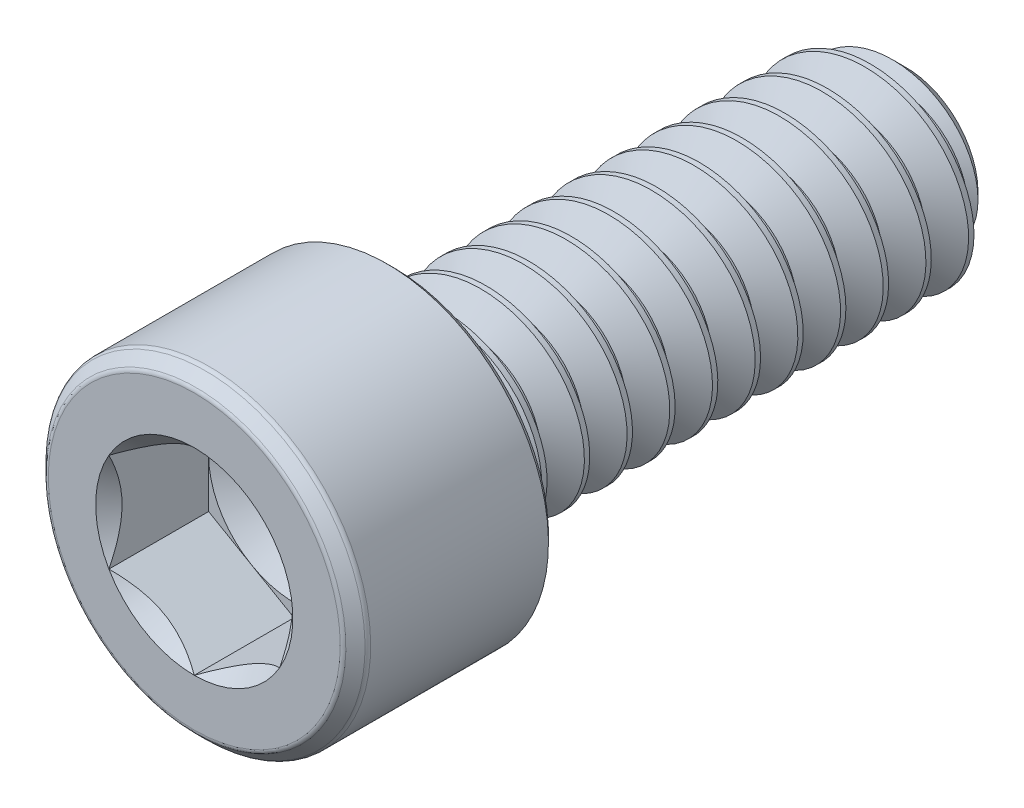
SolidWorks part; units mm, degrees
ref_plane "Front Plane" through (0, 0, 0) normal (0, 0, 1) x (1, 0, 0)
ref_plane "Top Plane" through (0, 0, 0) normal (0, 1, 0) x (1, 0, 0)
ref_plane "Right Plane" through (0, 0, 0) normal (1, 0, 0) x (0, 0, -1)
sketch "Sketch1" plane through (0, 0, 0) normal (1, 0, 0) x (0, 0, -1)
  line L0 (-3.3084, 0) -> (3.3084, 0) construction
  line L1 (-3.3084, 0) -> (-3.3084, 1.4986) construction
  line L2 (-3.3084, 1.4986) -> (-1.4541, 1.4986) construction
  line L3 (-1.4541, 1.4986) -> (-1.4541, 0.9271) construction
  line L4 (-1.4541, 0.9271) -> (3.0506, 0.9271) construction
  line L5 (3.2835, 0.9701) -> (3.482, 0.6264) construction
  line L6 (3.482, 0.6264) -> (3.6804, 0.9701) construction
  line L7 (3.6804, 0.9701) -> (3.2835, 0.9701) construction
  line L8 (3.0506, 0.9271) -> (3.3084, 0.6693) construction
  line L9 (3.3084, 0.6693) -> (3.3084, 0) construction
  line L10 (3.3084, 0.9271) -> (3.6556, 0.9271) construction
  line L11 (3.482, 0.9701) -> (3.482, 0.9271) construction
  line L12 (3.482, 0.9271) -> (3.482, 0.6693) construction
  line L13 (3.482, 0.6693) -> (3.482, 0.6264) construction
  line L14 (3.4572, 0.6693) -> (3.5068, 0.6693) construction
  line L15 (3.2959, 0.9486) -> (3.668, 0.9486) construction
  line L16 (3.5068, 0.6693) -> (3.668, 0.9486) construction
  line L17 (3.4572, 0.6693) -> (3.2959, 0.9486) construction
  line L18 (-3.3084, 0.7938) -> (-2.3813, 0.7938) construction
  line L19 (-2.3813, 0.7938) -> (-2.3813, 0) construction
  line L20 (1.9193, 0.9271) -> (1.9193, -0.9271) construction
  point P20 (3.482, 0.9486)
  point P22 (1.9193, -0.9271)
  point P28 (1.9193, 0)
  point P29 (3.0506, -0.9271)
  point P30 (-1.9177, 1.4986)
  point P31 (3.1814, 0)
  point P33 (-1.3271, 0)
  dimension "Length" = 4.7625
  dimension "Head Height" = 1.8542
  dimension "D1" = 45
  dimension "Thread Pitch" = 0.3969
  dimension "D3" = 0.0496
  dimension "D4" = 1.3891
  dimension "D5" = 0.9271
  dimension "D2" = 1.3906
  dimension "Head Diameter" = 2.9972
  dimension "Drive Size" = 1.5875
  dimension "Screw Size Decimal Equivalent" = 1.8542
  dimension "D6" = 4.6355
  dimension "D7" = 4.6355
sketch "Sketch3" plane through (0, 0, 0) normal (1, 0, 0) x (0, 0, -1)
  line L0 (-3.3084, 1.357) -> (-3.3084, 0.7938)
  line L1 (-3.3084, 0.7938) -> (-2.3813, 0.7938)
  line L2 (-2.3813, 0.7938) -> (-2.3813, 0)
  line L3 (-2.3813, 0) -> (3.3084, 0)
  line L4 (3.3084, 0) -> (3.3084, 0.6693)
  line L5 (3.3084, 0.6693) -> (3.0506, 0.9271)
  line L6 (3.0506, 0.9271) -> (-1.3383, 0.9271)
  line L7 (-1.4541, 1.043) -> (-1.4541, 1.4387)
  line L8 (-1.5141, 1.4986) -> (-3.1667, 1.4986)
  line L9 (-3.293, 1.3941) -> (-3.2038, 1.4832)
  line L11 (-3.3084, 1.4986) -> (-1.4541, 1.4986) construction
  line L14 (-1.5141, 1.4986) -> (-1.4541, 1.4387)
  arc A0 (-3.2038, 1.4832) -> (-3.1667, 1.4986) centre (-3.1667, 1.4461) cw
  arc A1 (-3.293, 1.3941) -> (-3.3084, 1.357) centre (-3.2559, 1.357) ccw
  arc A6 (-1.3383, 0.9271) -> (-1.4541, 1.043) centre (-1.3383, 1.043) cw
  point P25 (-3.3084, 1.3787)
  point P33 (-1.4541, 0.9271)
  dimension "D3" = 0.0525
  dimension "D10" = 0.1159
  dimension "D1" = 45
  dimension "D2" = 0.1199
  dimension "D7" = 45
  dimension "D8" = 0.0599
revolve "Revolve1" add sketch "Sketch3" angle 360 about L0
sketch "Sketch4" plane through (0, 0, 3.3084) normal (0, 0, 1) x (1, 0, 0)
  line L1 (0, 0.9165) -> (-0.7937, 0.4583)
  line L2 (-0.7937, 0.4583) -> (-0.7937, -0.4583)
  line L3 (-0.7937, -0.4583) -> (0, -0.9165)
  line L4 (0, -0.9165) -> (0.7937, -0.4583)
  line L5 (0.7937, -0.4583) -> (0.7937, 0.4583)
  line L6 (0.7937, 0.4583) -> (0, 0.9165)
  circle A0 centre (0, 0) radius 0.7937 construction
extrude "Cut-Extrude1" cut sketch "Sketch4" against normal up to vertex (0.9271 mm away) up to point (0, 0.7938, 2.3813)
sketch "Sketch5" plane through (0, 0, 3.3084) normal (0, 0, 1) x (1, 0, 0)
  circle A0 centre (0, 0) radius 0.9165
extrude "Cut-Extrude2" cut sketch "Sketch5" against normal up to next (0.9271 mm away) draft 45
sketch "Sketch10" plane through (0, 0, 2.3813) normal (0, 0, 1) x (1, 0, 0)
  line L0 (0.7937, 0.4583) -> (0.7937, -0.4583) construction
  circle A0 centre (0, 0) radius 0.7937
extrude "Cut-Extrude3" cut sketch "Sketch10" against normal through all draft 60
sketch "Sketch6" plane through (0, 0, -3.3084) normal (0, 0, -1) x (-1, 0, 0)
  circle A0 centre (0, 0) radius 0.9271 construction
  circle A1 centre (0, 0) radius 0.9271
curve "Helix/Spiral1" pitch 0.3969 height 5.1594 turns 13
ref_plane "Plane1" through (0, 0, 1.3383) normal (0, 0, 1) x (1, 0, 0)
split "Split1" trim tools "Plane1" bodies to split 112 resulting bodies 118 119
sketch "Sketch7" plane through (0, 0, 0) normal (1, 0, 0) x (0, 0, -1)
  line L0 (3.4572, 0.6693) -> (3.5068, 0.6693)
  line L8 (3.2959, 0.9486) -> (3.668, 0.9486)
  line L9 (3.668, 0.9486) -> (3.5068, 0.6693)
  line L11 (3.4572, 0.6693) -> (3.2959, 0.9486)
sweep "Cut-Sweep1" cut profiles "Sketch7" path "Helix/Spiral1" align with end faces yes
sketch "Sketch11" plane through (0, 0, 0) normal (1, 0, 0) x (0, 0, -1)
  line L2 (-1.4541, 0.9271) -> (3.0506, 0.9271) construction
  line L4 (-1.3383, 0.9271) -> (-0.4112, 0)
  line L5 (-3.3084, 0) -> (3.3084, 0) construction
  line L9 (-1.923, 0.9271) -> (-1.923, 0)
  line L10 (-1.923, 0) -> (-0.4112, 0)
  line L12 (-1.923, 0.9271) -> (-1.3383, 0.9271)
  dimension "D1" = 45
revolve "Revolve2" add sketch "Sketch11" angle 360 about L0
equation "\"D3@Sketch1\" = \"Thread Pitch@Sketch1\" / 8"
equation "\"D4@Sketch1\" = \"Thread Pitch@Sketch1\" * 3.5"
equation "\"D3@Helix/Spiral1\"=\"Length@Sketch1\" +( \"Thread Pitch@Sketch1\")"
equation "\"D4@Helix/Spiral1\" = \"Thread Pitch@Sketch1\""
equation "\"D5@Sketch1\"=\"Head Height@Sketch1\"*0.5"
equation "\"D2@Sketch3\"=\"Head Diameter@Sketch1\" /25"
equation "\"D3@Sketch3\"=\"D2@Sketch3\"*0.4375"
equation "\"D2@Sketch1\"=\"Head Height@Sketch1\"*0.75"
equation "\"D8@Sketch3\"=\"D2@Sketch3\"*0.5"
equation "\"D10@Sketch3\"=\"Screw Size Decimal Equivalent@Sketch1\"*0.0625"
equation "\"D7@Sketch1\"=\"Screw Size Decimal Equivalent@Sketch1\"*2.5"
equation "\"D6@Sketch1\"=\"D7@Sketch1\""
equation "\"D3@Sketch1\"=\"Thread Pitch@Sketch1\"/8"
